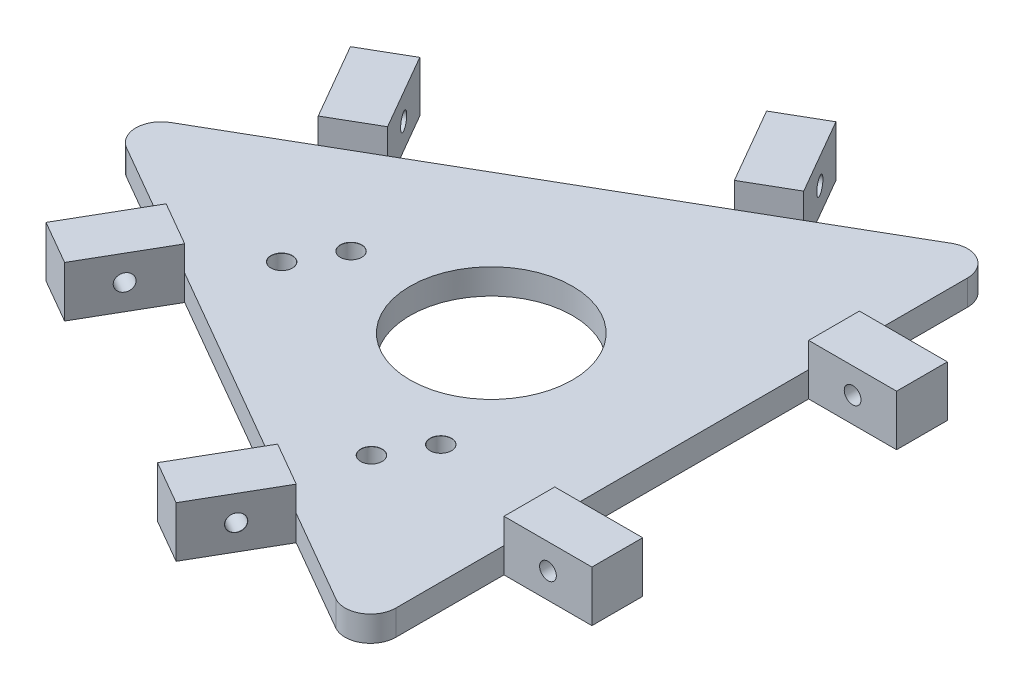
SolidWorks part; units mm, degrees
material "ABS"
ref_plane "Front" through (0, 0, 0) normal (0, 0, 1) x (1, 0, 0)
ref_plane "Top" through (0, 0, 0) normal (0, 1, 0) x (1, 0, 0)
ref_plane "Right" through (0, 0, 0) normal (1, 0, 0) x (0, 0, -1)
sketch "Sketch2" plane through (0, 0, 0) normal (0, 1, 0) x (0, 0, -1)
  line L0 (0, 0) -> (0, 70) construction
  line L1 (0, 0) -> (-60.6218, -35) construction
  line L2 (-60.6218, -30) -> (-49.976, -11.5609)
  line L3 (4.3301, 67.5) -> (14.976, 49.0609)
  line L4 (56.2917, -37.5) -> (35, -37.5)
  line L5 (0, 0) -> (-23.8157, 13.75) construction
  line L9 (-49.976, -11.5609) -> (-64.976, -2.9006)
  line L10 (-44.976, -2.9006) -> (-59.976, 5.7596)
  line L11 (-64.976, -2.9006) -> (-59.976, 5.7596)
  line L12 (-19.976, 40.4006) -> (-34.976, 49.0609)
  line L13 (-29.976, 57.7211) -> (-34.976, 49.0609)
  line L14 (-14.976, 49.0609) -> (-29.976, 57.7211)
  line L17 (14.976, 49.0609) -> (29.976, 57.7211)
  line L18 (29.976, 57.7211) -> (34.976, 49.0609)
  line L19 (19.976, 40.4006) -> (34.976, 49.0609)
  line L20 (44.976, -2.9006) -> (59.976, 5.7596)
  line L21 (64.976, -2.9006) -> (59.976, 5.7596)
  line L22 (49.976, -11.5609) -> (64.976, -2.9006)
  line L25 (35, -37.5) -> (35, -54.8205)
  line L26 (35, -54.8205) -> (25, -54.8205)
  line L27 (25, -37.5) -> (25, -54.8205)
  line L28 (-35, -37.5) -> (-35, -54.8205)
  line L29 (-35, -54.8205) -> (-25, -54.8205)
  line L30 (-25, -37.5) -> (-25, -54.8205)
  line L32 (-44.976, -2.9006) -> (-19.976, 40.4006)
  line L33 (-14.976, 49.0609) -> (-4.3301, 67.5)
  line L34 (19.976, 40.4006) -> (44.976, -2.9006)
  line L35 (49.976, -11.5609) -> (60.6218, -30)
  line L36 (25, -37.5) -> (-25, -37.5)
  line L37 (-35, -37.5) -> (-56.2917, -37.5)
  line L38 (-49.976, -11.5609) -> (-44.976, -2.9006)
  line L39 (-14.976, 49.0609) -> (-19.976, 40.4006)
  line L40 (14.976, 49.0609) -> (19.976, 40.4006)
  line L41 (49.976, -11.5609) -> (44.976, -2.9006)
  line L42 (35, -37.5) -> (25, -37.5)
  line L43 (-35, -37.5) -> (-25, -37.5)
  line L46 (-21.0862, -18.0213) -> (-18.0112, -12.6952) construction
  line L47 (5.0638, 27.2718) -> (1.9888, 21.9458) construction
  line L50 (-21.0862, -18.0213) -> (-18.0112, -12.6952)
  line L51 (5.0638, 27.2718) -> (1.9888, 21.9458)
  line L57 (-11.7414, -2.8357) -> (-12.1744, -2.5857) construction
  line L58 (2.5964, 21.9981) -> (-17.7527, -13.2476) construction
  line L59 (-4.5724, 10.5814) -> (-17.7612, -12.2622) construction
  arc A0 (-60.6218, -30) -> (-56.2917, -37.5) centre (-56.2917, -32.5) ccw
  arc A1 (60.6218, -30) -> (56.2917, -37.5) centre (56.2917, -32.5) cw
  arc A2 (4.3301, 67.5) -> (-4.3301, 67.5) centre (0, 65) ccw
  circle A3 centre (-56.2917, -32.5) radius 5 construction
  point P50 (0, 0)
  dimension "D4" = 10
  dimension "D1" = 90
  dimension "D2" = 50
  dimension "D3" = 70
  dimension "D7" = 10
  dimension "D8" = 15
extrude "Boss-Extrude1" add sketch "Sketch2" along normal blind 5 contours L3 A2 L33 L39 L32 L38 L2 A0 L37 L43 L36 L42 L4 A1 L35 L41 L34 L40
extrude "Boss-Extrude3" add sketch "Sketch2<7>" along normal blind 10 contours L41 L22 L21 L20 | L17 L40 L19 L18 region at (-49.0609, 0, -24.976) region at (2.9006, 0, -54.976)
sketch "Sketch2<7>" plane through (0, 0, 0) normal (0, 1, 0) x (0, 0, -1) same geometry as "Sketch2"
sketch "Sketch10" plane through (-30.3109, 0, 17.5) normal (-0.866, 0, 0.5) x (0.5, 0, 0.866)
  line L1 (-46.1603, 5) -> (-37.5, 5) construction
  line L2 (-54.8205, 5) -> (-46.1603, 5) construction
  line L9 (-54.8205, 10) -> (-54.8205, 0) construction
  line L11 (-46.1603, 5) -> (-46.1603, 10) construction
  line L12 (-37.5, 10) -> (-54.8205, 10) construction
  line L14 (-46.1603, 5) -> (-46.1603, 0) construction
  line L15 (-37.5, 0) -> (-54.8205, 0) construction
  point P0 (-46.1603, 5)
  dimension "D1" = 180
hole_wizard "Tap Drill for M4 Tap1" positions "Sketch10" profile "Sketch11" hole size "M4" standard "ISO" end condition through all
sketch "Sketch11" plane through (-53.391, 5, -22.476) normal (0, 1, 0) x (0.5, 0, 0.866)
  line L0 (0, 0) -> (0, 99.9639)
  line L1 (0, 99.9639) -> (1.65, 99.9639)
  line L2 (1.65, 99.9639) -> (1.65, 0.025)
  line L3 (1.65, 0.025) -> (1.675, 0)
  line L5 (1.675, 0) -> (0, 0)
  line L6 (-1.65, 0.025) -> (-1.675, 0) construction
  line L11 (0, -6.35) -> (0, 107.95) construction
  dimension "Thru Hole Dia." = 3.3
  dimension "Thru Hole Depth" = 99.9639
  dimension "Near C'Sink Dia." = 3.35
  dimension "Near C'Sink Angle" = 90
pattern_circular "CirPattern1" count 3 every 120 about axis through (0, 5, 0) along (0, 1, 0) of "Boss-Extrude3", "Tap Drill for M4 Tap1"
sketch "Sketch13" plane through (0, 0, 0) normal (0, -1, 0) x (1, 0, 0)
  line L0 (-18.75, 32.476) -> (0, 0) construction
  line L1 (0, 0) -> (37.5, 0) construction
  line L2 (2.9006, 44.976) -> (-40.4006, 19.976) construction
  line L3 (37.5, -25) -> (37.5, 25) construction
  line L4 (-40.4006, -19.976) -> (2.9006, -44.976) construction
  line L5 (0, 0) -> (-18.75, -32.476) construction
  circle A1 centre (0.007, 0.0121) radius 16
  circle A2 centre (0, 0) radius 7.6921 construction
  point P3 (0, 0)
  point P4 (-18.75, 32.476)
  point P5 (37.5, 0)
  point P8 (-18.75, -32.476)
extrude "Cut-Extrude1" cut sketch "Sketch13" against normal through all contours A1
sketch "Sketch16" plane through (0, 5, 0) normal (0, 1, 0) x (1, 0, 0)
  arc A0 (-29.7754, -0.0725) -> (-28.5754, 2.0059) centre (-27.7898, 0.1667) ccw construction
  arc A1 (-34.7754, -8.7328) -> (-33.5754, -6.6543) centre (-32.7898, -8.4936) ccw construction
  arc A2 (16.0249, -23.7441) -> (14.8249, -25.8225) centre (14.0392, -23.9833) ccw construction
  arc A3 (11.0249, -32.4043) -> (9.8249, -34.4828) centre (9.0392, -32.6436) ccw construction
  arc A4 (-29.7754, -0.0725) -> (-28.5754, 2.0059) centre (-27.7898, 0.1667) ccw
  arc A5 (-34.7754, -8.7328) -> (-33.5754, -6.6543) centre (-32.7898, -8.4936) ccw
  arc A6 (16.0249, -23.7441) -> (14.8249, -25.8225) centre (14.0392, -23.9833) ccw
  arc A7 (11.0249, -32.4043) -> (9.8249, -34.4828) centre (9.0392, -32.6436) ccw
  point P0 (-27.7898, 0.1667)
  point P3 (-32.7898, -8.4936)
  point P6 (14.0392, -23.9833)
  point P9 (9.0392, -32.6436)
hole_wizard "Tap Drill for M5 Tap1" positions "Sketch16" profile "Sketch18" hole size "M5" standard "ISO" end condition through all
sketch "Sketch18" plane through (-27.7898, 5, -0.1667) normal (1, 0, 0) x (0, 0, 1)
  line L0 (0, 0) -> (0, 5)
  line L1 (0, 5) -> (2.1, 5)
  line L2 (2.1, 5) -> (2.1, 0.025)
  line L3 (2.1, 0.025) -> (2.125, 0)
  line L5 (2.125, 0) -> (0, 0)
  line L6 (-2.1, 0.025) -> (-2.125, 0) construction
  line L11 (0, -6.35) -> (0, 107.95) construction
  dimension "Thru Hole Dia." = 4.2
  dimension "Thru Hole Depth" = 5
  dimension "Near C'Sink Dia." = 4.25
  dimension "Near C'Sink Angle" = 90
